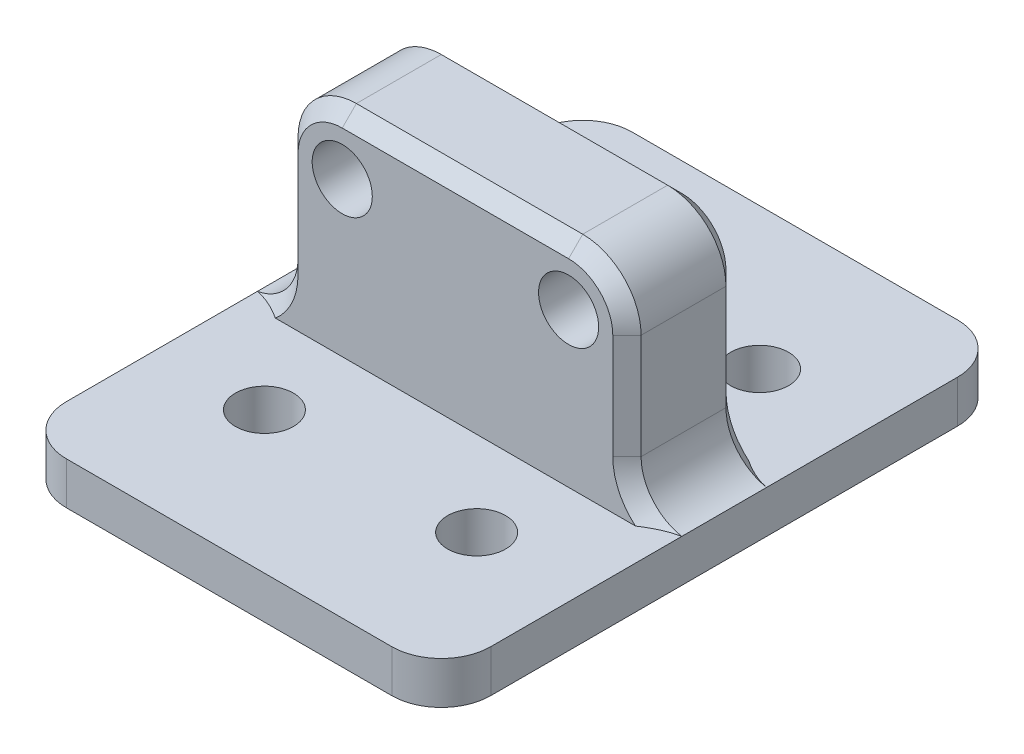
SolidWorks part; units mm, degrees
ref_plane "Front Plane" through (0, 0, 0) normal (0, 0, 1) x (1, 0, 0)
ref_plane "Top Plane" through (0, 0, 0) normal (0, 1, 0) x (1, 0, 0)
ref_plane "Right Plane" through (0, 0, 0) normal (1, 0, 0) x (0, 0, -1)
sketch "Sketch1" plane through (0, 0, 0) normal (0, 1, 0) x (1, 0, 0)
  line L1 (-15, -20) -> (15, -20)
  line L2 (-15, -20) -> (-15, 20)
  line L3 (-15, 20) -> (15, 20)
  line L4 (15, -20) -> (15, 20)
  line L5 (-15, -20) -> (15, 20) construction
  line L6 (-15, 20) -> (15, -20) construction
  point P0 (0, 0)
  line B0 (-7.5, -10) -> (7.5, -10) construction
  line B1 (-7.5, -10) -> (-7.5, 10) construction
  line B2 (-7.5, 10) -> (7.5, 10) construction
  line B3 (7.5, -10) -> (7.5, 10) construction
  circle B4 centre (-7.5, 10) radius 2.05
  circle B5 centre (7.5, 10) radius 2.05
  circle B6 centre (-7.5, -10) radius 2.05
  circle B7 centre (7.5, -10) radius 2.05
  dimension "D1" = 30
  dimension "D2" = 40
sketch_block_instance "Block1-1"
sketch_block "Block1" parameters "D1"=4.1, "D2"=20, "D3"=15
extrude "Boss-Extrude1" add sketch "Sketch1" along normal blind 3 contours B5 | L1 L4 L3 L2 B7 B6 B5 B4 | L2 L1 L4 L3 region at (0, 0, 0) region at (7.5, 0, -10)
fillet "Fillet1" radius 3.5 4 edges at (-15, 1.5, 20) (15, 1.5, -20) (-15, 1.5, -20) (15, 1.5, 20)
sketch "Sketch2" plane through (0, 0, 0) normal (0, 0, 1) x (1, 0, 0)
  line L0 (0, 0) -> (12.125, 0)
  line L2 (12.125, 0) -> (12.125, 13.875)
  line L3 (8, 18) -> (-8, 18)
  line L4 (-12.125, 13.875) -> (-12.125, 0)
  line L5 (-12.125, 0) -> (0, 0)
  line L6 (-8, 13.875) -> (8, 13.875) construction
  arc A1 (-8, 18) -> (-12.125, 13.875) centre (-8, 13.875) ccw
  arc A2 (8, 18) -> (12.125, 13.875) centre (8, 13.875) cw
  circle A3 centre (-8, 13.875) radius 2.125
  circle A4 centre (8, 13.875) radius 2.125
  point P11 (0, 18)
  point P16 (0, 13.875)
  dimension "D2" = 4.25
  dimension "D3" = 2
  dimension "D1" = 16
  dimension "D4" = 18
extrude "Boss-Extrude2" add sketch "Sketch2" along normal mid plane 8
fillet "Fillet2" radius 3.5 2 edges at (12.125, 3, 0) (-12.125, 3, 0)
chamfer "Chamfer1" distance 1 angle 45 14 edges at (12.9382, 4.2007, -4) (-12.9382, 4.2007, -4) (12.125, 10.1594, -4) (-12.125, 10.1594, -4) (10.9168, 16.7918, -4) (-10.9168, 16.7918, -4) (0, 18, -4) (12.9382, 4.2007, 4) (-12.9382, 4.2007, 4) (12.125, 10.1594, 4) (-12.125, 10.1594, 4) (10.9168, 16.7918, 4) (-10.9168, 16.7918, 4) (0, 18, 4)
extrude "Cut-Extrude2" cut sketch "Sketch1<3>" against normal through all and the other way through all contours B4 | B5 | B7 | B6 region at (-7.5, 0, -10) region at (7.5, 0, -10) region at (-7.5, 0, 10) region at (7.5, 0, 10)
sketch "Sketch1<3>" plane through (0, 0, 0) normal (0, 1, 0) x (1, 0, 0) same geometry as "Sketch1"
